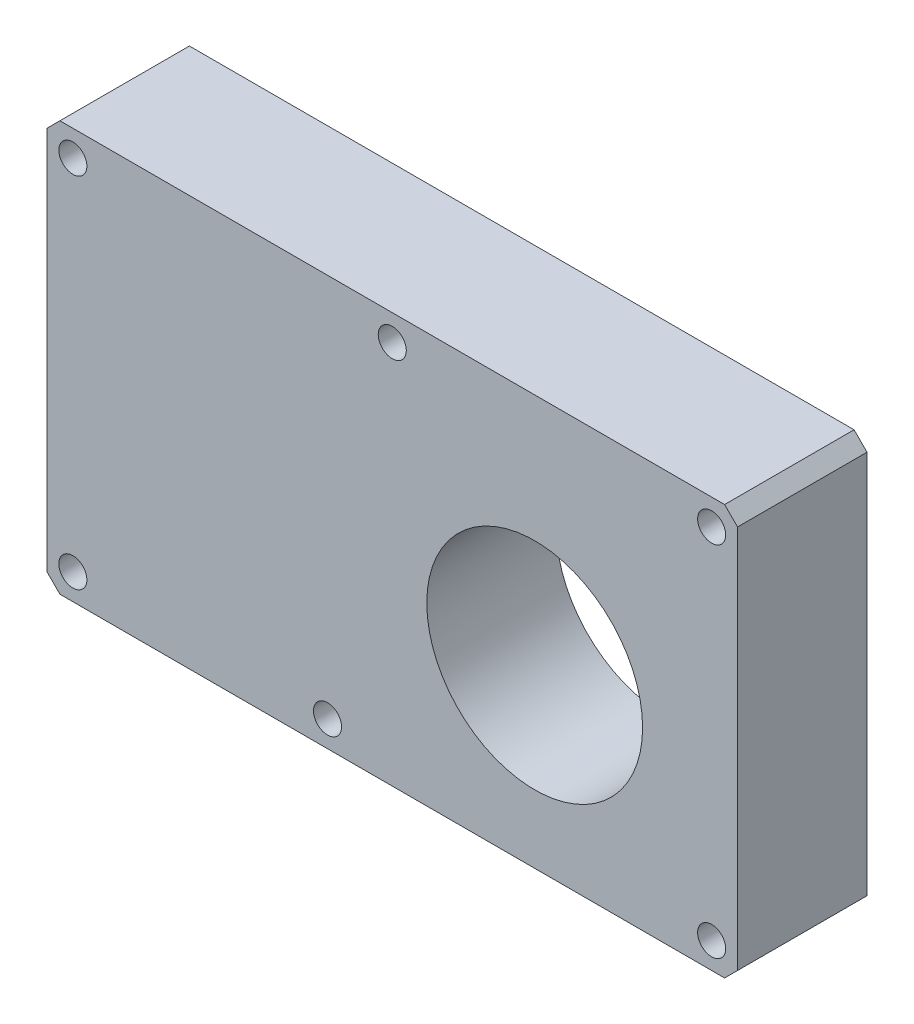
SolidWorks part; units mm, degrees
ref_plane "前视基准面" through (0, 0, 0) normal (0, 0, 1) x (1, 0, 0)
ref_plane "上视基准面" through (0, 0, 0) normal (0, 1, 0) x (1, 0, 0)
ref_plane "右视基准面" through (0, 0, 0) normal (1, 0, 0) x (0, 0, -1)
other "Configuration Table"
sketch "草图1" plane through (0, 0, 0) normal (0, 0, 1) x (1, 0, 0)
  line L1 (0, 0) -> (160, 0)
  line L2 (0, 0) -> (0, -95)
  line L3 (0, -95) -> (160, -95)
  line L4 (160, 0) -> (160, -95)
  dimension "D1" = 160
  dimension "D2" = 95
extrude "凸台-拉伸1" add sketch "草图1" along normal blind 30
chamfer "倒角1" distance 3 angle 45 4 edges at (160, -95, 15) (160, 0, 15) (0, -95, 15) (0, 0, 15)
sketch "草图2" plane through (0, 0, 0) normal (0, 0, -1) x (-1, 0, 0)
  circle A0 centre (-113, -54.25) radius 25
  dimension "D1" = 50
extrude "切除-拉伸1" cut sketch "草图2" against normal through all
hole_wizard "M8 螺纹孔1" positions "草图5" profile "草图4" tap size "M8" standard "GB"
sketch "草图5" plane through (0, 0, 0) normal (0, 0, -1) x (-1, 0, 0)
  point P0 (-143, -24.5)
  point P3 (-83, -24.5)
  point P6 (-83, -84.5)
  point P9 (-143, -84.5)
cosmetic thread "孔螺蚊线1" parameters "D2"=8
cosmetic thread "孔螺蚊线2" parameters "D2"=8
cosmetic thread "孔螺蚊线3" parameters "D2"=8
cosmetic thread "孔螺蚊线4" parameters "D2"=8
sketch "草图4" plane through (143, -24.5, 0) normal (1, 0, 0) x (0, 1, 0)
  line L0 (0, 0) -> (0, 22.0429)
  line L1 (0, 22.0429) -> (3.4, 20)
  line L2 (3.4, 20) -> (3.4, 0)
  line L5 (3.4, 0) -> (0, 0)
  line L10 (0, 22.0429) -> (-3.4, 20) construction
  line L11 (0, -6.35) -> (0, 107.95) construction
  dimension "螺纹孔钻头直径" = 6.8
  dimension "螺纹孔钻头深度" = 20
  dimension "导头角度" = 118
sketch "草图6" plane through (0, 0, 0) normal (0, 0, -1) x (-1, 0, 0)
  line L0 (-160, -92) -> (-160, -3) construction
  line L1 (-157, 0) -> (-3, 0) construction
  line L2 (-3, -95) -> (-157, -95) construction
  line L3 (0, -3) -> (0, -92) construction
  circle A0 centre (-154, -6) radius 5.25
  circle A1 centre (-80, -6) radius 5.25
  circle A2 centre (-6, -6) radius 5.25
  circle A4 centre (-6, -89) radius 5.25
  circle A5 centre (-154, -89) radius 5.25
  circle A6 centre (-65, -89) radius 5.25
  circle A7 centre (-80, -89) radius 5.25 [skipped]
  dimension "D1" = 10.5
  dimension "D6" = 10.5
  dimension "D2" = 6
  dimension "D3" = 6
  dimension "D7" = 6
  dimension "D8" = 65
  dimension "D4" = 3
  dimension "D5" = 2
extrude "切除-拉伸2" cut sketch "草图6" against normal blind 15
sketch "草图7" plane through (0, 0, 15) normal (0, 0, -1) x (-1, 0, 0)
  circle A0 centre (-154, -6) radius 5.25 construction
  circle A1 centre (-154, -6) radius 5.25 construction
  circle A2 centre (-154, -6) radius 3.25
  circle A3 centre (-80, -6) radius 3.25
  circle A4 centre (-6, -6) radius 3.25
  circle A6 centre (-6, -89) radius 3.25
  circle A7 centre (-154, -89) radius 3.25
  circle A8 centre (-65, -89) radius 3.25
  circle A9 centre (-65, -89) radius 5.25
  circle A10 centre (-65, -89) radius 5.25 construction
  circle A11 centre (-80, -89) radius 3.25 [skipped]
  point P5 (0, 0)
  dimension "D1" = 6.5
  dimension "D5" = 6.5
  dimension "D4" = 0
  dimension "D2" = 3
  dimension "D3" = 2
extrude "切除-拉伸3" cut sketch "草图7" against normal through all
